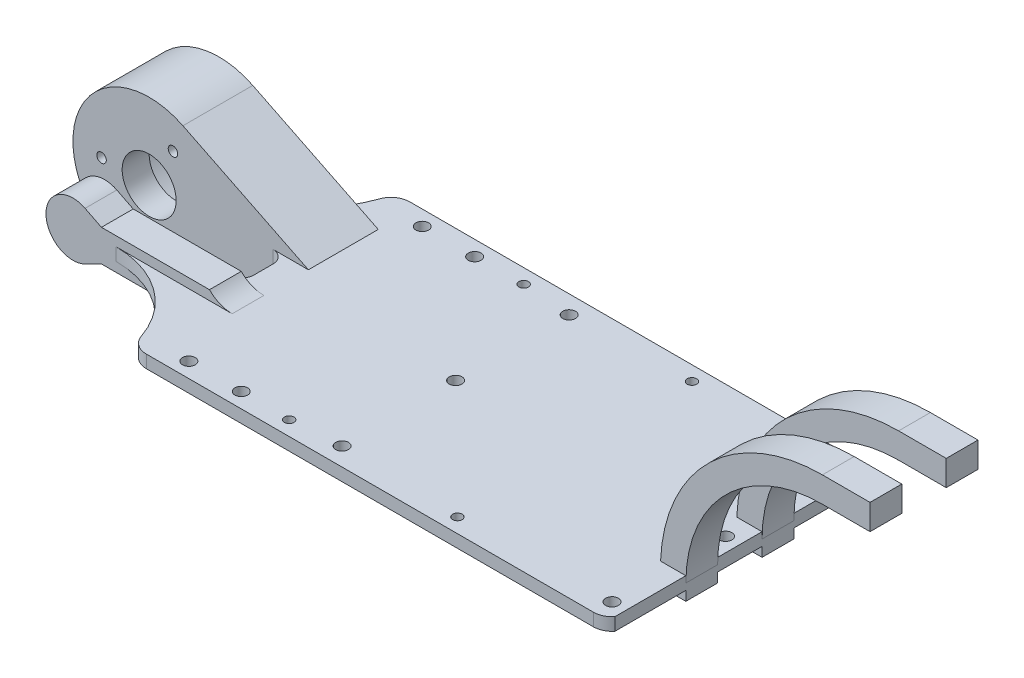
SolidWorks part; units mm, degrees
note: The reader was unsure of these and kept them because the rebuilt part matched: shared geometry of "Sketch1<3>", "Sketch9<4>", "Sketch6<3>", "Sketch14<2>".
ref_plane "Front Plane" through (0, 0, 0) normal (0, 0, 1) x (1, 0, 0)
ref_plane "Top Plane" through (0, 0, 0) normal (0, 1, 0) x (1, 0, 0)
ref_plane "Right Plane" through (0, 0, 0) normal (1, 0, 0) x (0, 0, -1)
sketch "Sketch1" plane through (0, 0, 0) normal (0, 1, 0) x (1, 0, 0)
  line L0 (0, 121.3543) -> (0, -121.3543) construction
  line L1 (-75, -41.5) -> (75, -41.5)
  line L2 (-75, -41.5) -> (-75, 41.5)
  line L3 (-75, 41.5) -> (75, 41.5)
  line L4 (75, -41.5) -> (75, 41.5)
  line L5 (-75, -41.5) -> (75, 41.5) construction
  line L6 (-75, 41.5) -> (75, -41.5) construction
  line L7 (-246.33, 0) -> (246.33, 0) construction
  line L8 (-75, 7) -> (-124, 7)
  line L9 (-124, 7) -> (-124, 17)
  line L10 (-124, 17) -> (-75, 17)
  line L11 (-124, -17) -> (-75, -17)
  line L12 (-124, -7) -> (-124, -17)
  line L13 (-75, -7) -> (-124, -7)
  line L14 (-118, 46.0679) -> (-118, -44.6537) construction
  line L15 (124, -17) -> (75, -17)
  line L16 (124, -7) -> (124, -17)
  line L17 (75, -7) -> (124, -7)
  line L18 (75, 7) -> (124, 7)
  line L19 (124, 7) -> (124, 17)
  line L20 (124, 17) -> (75, 17)
  circle A0 centre (70.5, 35.75) radius 2
  circle A1 centre (70.5, 0) radius 2
  circle A2 centre (70.5, -35.75) radius 2
  circle A3 centre (-14.5, -35.75) radius 2
  circle A4 centre (-14.5, 0) radius 2
  circle A5 centre (-14.5, 35.75) radius 2
  circle A6 centre (-30, -36.93) radius 1.5
  circle A7 centre (23, -36.93) radius 1.5
  circle A8 centre (23, 36.93) radius 1.5
  circle A9 centre (-30, 36.93) radius 1.5
  point P0 (0, 0)
  point P8 (0, 0)
  point P11 (0, 0)
  dimension "D7" = 4
  dimension "D8" = 4
  dimension "D9" = 4
  dimension "D10" = 4
  dimension "D11" = 4
  dimension "D12" = 4
  dimension "D13" = 4.57
  dimension "D15" = 3
  dimension "D16" = 4.57
  dimension "D17" = 3
  dimension "D1" = 83
  dimension "D2" = 150
  dimension "D3" = 14
  dimension "D4" = 10
  dimension "D5" = 43
  dimension "D6" = 6
  dimension "D14" = 45
  dimension "D18" = 98
extrude "Boss-Extrude1" add sketch "Sketch1" along normal mid plane 10 contours L10 L9 L8 L2 | L2 L13 L12 L11 | L19 L20 L4 L18 | L17 L4 L15 L16
sketch "Sketch2" plane through (0, 0, -17) normal (0, 0, -1) x (-1, 0, 0)
  line L0 (-124, -5) -> (-75, -5) construction
  line L1 (-124, 5) -> (-75, 5) construction
  line L2 (-124, 5) -> (-124, -5) construction
  line L6 (0, 69.849) -> (0, -80.9232) construction
  line L10 (-118, 5) -> (-118, 9.5057)
  line L11 (-118, 9.5057) -> (-152.7264, 9.5057)
  line L12 (-152.7264, 9.5057) -> (-152.7264, -6.9043)
  line L13 (-152.7264, -6.9043) -> (-118, -6.9043)
  line L14 (-118, -6.9043) -> (-118, -5)
  line L15 (118, 5) -> (118, 9.5057)
  line L16 (118, 9.5057) -> (152.7264, 9.5057)
  line L17 (152.7264, 9.5057) -> (152.7264, -6.9043)
  line L18 (152.7264, -6.9043) -> (118, -6.9043)
  line L19 (118, -6.9043) -> (118, -5)
  arc A0 (-118, -5) -> (-118, 5) centre (-118, 0) cw
  circle A1 centre (-118, 0) radius 2
  circle A2 centre (118, 0) radius 2
  arc A3 (118, -5) -> (118, 5) centre (118, 0) ccw
  dimension "D2" = 4
  dimension "D1" = 6
extrude "Cut-Extrude7" cut sketch "Sketch2" against normal through all both and the other way through all
extrude "Boss-Extrude2" add sketch "Sketch1<3>" along normal mid plane 4 contours L1 L4 L3 L2
sketch "Sketch1<3>" plane through (0, 0, 0) normal (0, 1, 0) x (1, 0, 0) same geometry as "Sketch1"
fillet "Fillet1" radius 10 4 edges at (-75, 2, -12) (-75, 2, 12) (75, 2, 12) (75, 2, -12)
sketch "Sketch3" plane through (0, -2, 0) normal (0, -1, 0) x (1, 0, 0)
  line L0 (-75, 17) -> (75, 17)
  line L1 (-75, 7) -> (75, 7)
  line L2 (-75, -7) -> (75, -7)
  line L3 (-75, -17) -> (75, -17)
  line L4 (-75, -17) -> (-75, -7)
  line L5 (75, -17) -> (75, -7)
  line L6 (75, 7) -> (75, 17)
  line L7 (-75, 7) -> (-75, 17)
extrude "Boss-Extrude3" add sketch "Sketch3" along normal up to surface (3 mm away) up to face at (96.5, -5, 13.25)
fillet "Fillet2" radius 30 4 edges at (-75, 0, 17) (-75, 0, -17) (75, 0, 17) (75, 0, -17)
fillet "Fillet3" radius 4 4 edges at (75, 0, 7) (75, 0, -7) (-75, 0, 7) (-75, 0, -7)
fillet "Fillet4" radius 6 4 edges at (75, 0, 41.5) (-75, 0, 41.5) (75, 0, -41.5) (-75, 0, -41.5)
sketch "Sketch4" plane through (0, 2, 0) normal (0, 1, 0) x (1, 0, 0)
  circle A0 centre (-45.25, -36.75) radius 2
  circle A1 centre (-61.75, -36.75) radius 2
  circle A2 centre (-45.25, 36.75) radius 2
  circle A3 centre (-61.75, 36.75) radius 2
extrude "Cut-Extrude8" cut sketch "Sketch4" against normal through all both and the other way through all
sketch "Sketch7" plane through (0, 0, -17) normal (0, 0, -1) x (-1, 0, 0)
  line L0 (118, 5) -> (75, 5) construction
  line L1 (94.8198, 5) -> (123.2507, 5)
  line L2 (94.8198, 5) -> (94.8198, -5.3108)
  line L3 (94.8198, -5.3108) -> (123.2507, -5.3108)
  line L4 (123.2507, 5) -> (123.2507, -5.3108)
extrude "Cut-Extrude11" cut sketch "Sketch7" against normal blind 10 and the other way blind 10
sketch "Sketch6" plane through (0, 0, -17) normal (0, 0, -1) x (-1, 0, 0)
  line L0 (118, 0) -> (173.2033, 0) construction
  line L1 (107.3708, 21.5179) -> (67.8586, 2)
  line L2 (107.3708, -21.5179) -> (67.8586, -2)
  line L4 (67.8586, 2) -> (67.8586, -2)
  circle A0 centre (118, 0) radius 8.5
  circle A1 centre (118, 0) radius 15 construction
  circle A2 centre (118, 0) radius 21.075
  circle A3 centre (118, 0) radius 24
  circle A4 centre (133, 0) radius 1.5
  circle A5 centre (110.5, 12.9904) radius 1.5
  circle A6 centre (110.5, -12.9904) radius 1.5
  line M5 (94.8198, -2) -> (-104.4915, -2)
  line M11 (-118, -5) -> (94.8198, -5)
  line M22 (94.8198, -5) -> (94.8198, -2)
  dimension "D1" = 48
  dimension "D2" = 42.15
  dimension "D3" = 30
  dimension "D4" = 17
  dimension "D5" = 120
  dimension "D7" = 3
  dimension "D8" = 3
  dimension "D9" = 3
  dimension "D6" = 120
extrude "Boss-Extrude4" add sketch "Sketch6" along normal blind 22 from surface at -10 contours A2 A6 A5 A4 A0 | A3 A2 M5 M22 M11 | A3 L2 M11 | A3 L1 L4 M5 | A3 L2 M5 M11 | A3 M5 M11 M22 starting at face at (116, 0, -7)
sketch "Sketch9" plane through (0, 0, 17) normal (0, 0, 1) x (1, 0, 0)
  line L2 (-114.1821, 7.5943) -> (-103.0542, 2)
  line L3 (-67.8586, 2) -> (-104.4915, 2) construction
  line L4 (-114.1821, -7.5943) -> (-103.0542, -2)
  line L5 (104.4915, -2) -> (-104.4915, -2) construction
  line L6 (-103.0542, -2) -> (-103.0542, 2)
  circle A0 centre (-118, 0) radius 6.3
  circle A1 centre (-118, 0) radius 8.5
  circle M4 centre (-118, 0) radius 2
  line M5 (104.4915, -2) -> (-104.4915, -2)
  line M6 (-104.4915, -2) -> (-104.4915, 2)
  line M7 (-104.4915, 2) -> (-67.8586, 2)
  line M9 (-75, 5) -> (-118, 5)
  arc M10 (-118, 5) -> (-118, -5) centre (-118, 0) ccw
  line M11 (-118, -5) -> (118, -5)
  dimension "D1" = 12.6
  dimension "D2" = 26.69
  dimension "D3" = 17
extrude "Boss-Extrude5" add sketch "Sketch9" along direction (0, 0, -1) on the side of the normal up to surface (10 mm away) from surface at -10 contours A1 L4 L2 M11 M5 M6 M7 M9 | A1 A0 M9 M11 | A0 M11 M9 M10 M4 | A0 M9 M11 M10 | A1 A0 M11 M9 | A1 L2 M9 | A1 L4 M11 | M4 starting at face at (-116, 0, 7)
extrude "Cut-Extrude12" cut sketch "Sketch9<4>" along normal blind 4.2 from surface at -10 contours A0 M9 M11 M10 | A0 M11 M9 M10 M4 | M4 starting at face at (-15.5518, 0.8972, 7)
sketch "Sketch9<4>" plane through (0, 0, 17) normal (0, 0, 1) x (1, 0, 0) same geometry as "Sketch9"
extrude "Cut-Extrude13" cut sketch "Sketch6<3>" against normal blind 13.5 from surface at 12 contours A2 A6 A5 A4 A0 starting at face at (-109, -12.9904, -29)
sketch "Sketch6<3>" plane through (0, 0, -17) normal (0, 0, -1) x (-1, 0, 0) same geometry as "Sketch6"
sketch "Sketch11" plane through (0, 2, 0) normal (0, 1, 0) x (1, 0, 0)
  line L1 (75, 41.5) -> (123, 41.5)
  line L2 (75, 41.5) -> (75, -41.5)
  line L3 (75, -41.5) -> (123, -41.5)
  line L4 (123, 41.5) -> (123, -41.5)
  line L6 (75, -3) -> (75, 3) construction
  line L7 (-70.3777, 41.5) -> (70.3777, 41.5) construction
  line L8 (-70.3777, -41.5) -> (70.3777, -41.5) construction
  line L9 (123, 7) -> (123, 17) construction
extrude "Cut-Extrude14" cut sketch "Sketch11" against normal through all both and the other way through all
sketch "Sketch14" plane through (0, 0, 0) normal (0, 0, 1) x (1, 0, 0)
  line L0 (118, 0) -> (75, 0) construction
  line L1 (75, 2) -> (75, -2) construction
  line L3 (67, 0) -> (75, 0)
  line L4 (118, 51) -> (118, 0) construction
  line L5 (118, 43) -> (133, 43)
  line L6 (133, 43) -> (133, 51)
  line L7 (133, 51) -> (118, 51)
  arc A0 (75, 0) -> (118, 43) centre (118, 0) cw
  arc A1 (67, 0) -> (118, 51) centre (118, 0) cw
  dimension "D1" = 43
  dimension "D2" = 8
  dimension "D3" = 15
extrude "Boss-Extrude6" add sketch "Sketch14" along normal up to surface (10 mm away) from surface at 7 up to face at (72.7203, 2.7602, 17) starting at face at (-111.7, 0, 7)
extrude "Boss-Extrude7" add sketch "Sketch14<2>" along normal up to surface (10 mm away) from surface
sketch "Sketch14<2>" plane through (0, 0, 0) normal (0, 0, 1) x (1, 0, 0) same geometry as "Sketch14"
